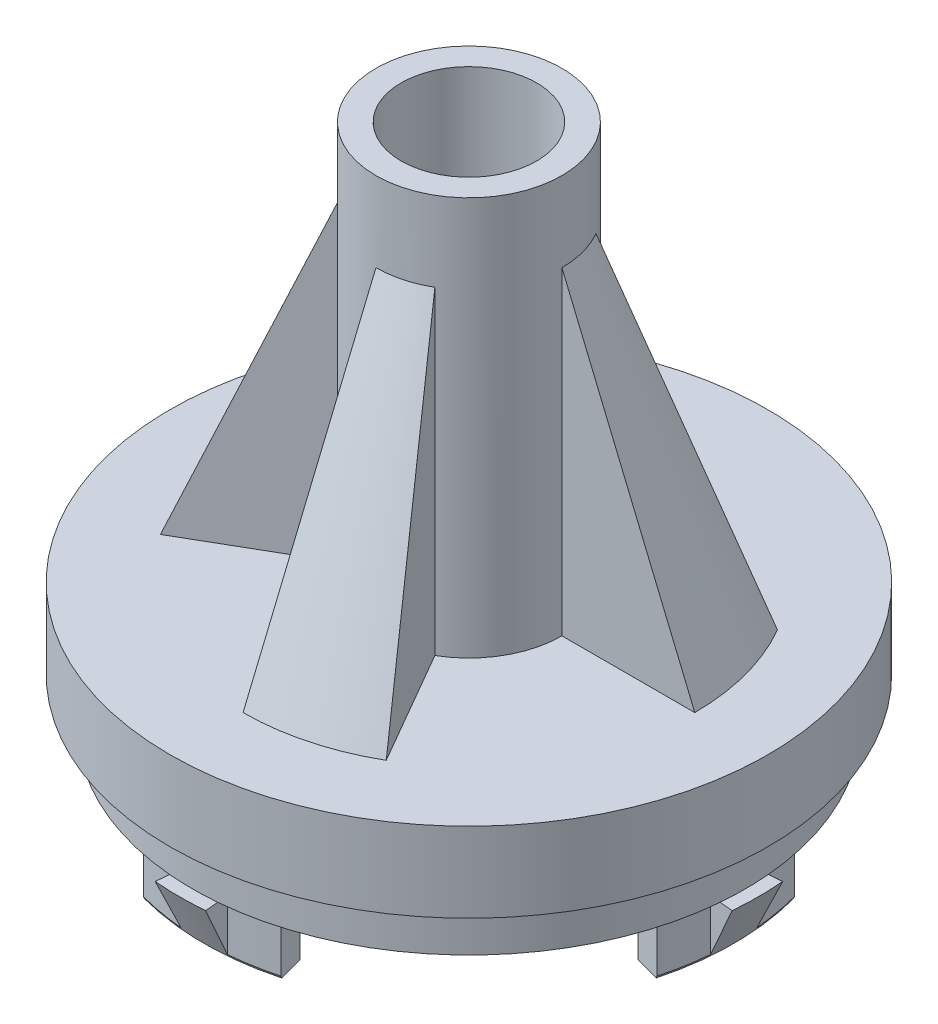
SolidWorks part; units mm, degrees
ref_plane "前视基准面" through (0, 0, 0) normal (0, 0, 1) x (1, 0, 0)
ref_plane "上视基准面" through (0, 0, 0) normal (0, 1, 0) x (1, 0, 0)
ref_plane "右视基准面" through (0, 0, 0) normal (1, 0, 0) x (0, 0, -1)
other "Configuration Table"
sketch "草图1" plane through (0, 0, 0) normal (0, 1, 0) x (1, 0, 0)
  circle A0 centre (0, 0) radius 10.4
  dimension "D1" = 20.8
extrude "凸台-拉伸1" add sketch "草图1" along normal blind 1.8
sketch "草图2" plane through (0, 1.8, 0) normal (0, 1, 0) x (1, 0, 0)
  circle A0 centre (0, 0) radius 11.25
  dimension "D1" = 22.5
extrude "凸台-拉伸2" add sketch "草图2" along normal blind 3
sketch "草图3" plane through (0, 4.8, 0) normal (0, 1, 0) x (1, 0, 0)
  circle A0 centre (0, 0) radius 3.5
  circle A1 centre (0, 0) radius 2.55
  circle A2 centre (0, 0) radius 1.5
  dimension "D1" = 7
  dimension "D2" = 5.1
  dimension "D3" = 3
extrude "凸台-拉伸3" add sketch "草图3" along normal blind 15 contours A0 A1 region at (-3.401, 4.8, 0)
extrude "切除-拉伸2" cut sketch "草图3<4>" against normal up to surface (4.8 mm away) contours A2 up to face at (0, 0, 10.4)
sketch "草图3<4>" plane through (0, 4.8, 0) normal (0, 1, 0) x (1, 0, 0) same geometry as "草图3"
sketch "草图6" plane through (0, 0, 0) normal (1, 0, 0) x (0, 0, -1)
  line L0 (0, 0) -> (0, 11.6571) construction
  line L1 (0, 0) -> (14.4338, 0) construction
  line L2 (3.5, 16.8) -> (8.5, 4.8)
  line L3 (3.5, 4.8) -> (3.5, 19.8) construction
  line L4 (11.25, 4.8) -> (-11.25, 4.8) construction
  line L5 (8.5, 4.8) -> (3.5, 4.8)
  line L6 (3.5, 4.8) -> (3.5, 16.8)
  line L7 (-8.5, 4.8) -> (-3.5, 4.8)
  line L8 (-3.5, 16.8) -> (-8.5, 4.8)
  line L9 (-3.5, 4.8) -> (-3.5, 16.8)
  dimension "D1" = 5
  dimension "D2" = 12
revolve "旋转3" add sketch "草图6" angle 30 about L0 region at (0, 8.8, -5.1667) region at (0, 8.8, 5.1667)
sketch "草图9" plane through (0, 0, 0) normal (0, 0, 1) x (1, 0, 0)
  line L0 (3.5, 4.8) -> (8.5, 4.8)
  line L1 (3.5, 16.8) -> (3.5, 4.8)
  line L2 (8.5, 4.8) -> (3.5, 16.8)
  line L3 (3.5, 4.8) -> (3.5, 19.8) construction
  line L4 (0, 0) -> (0, 22.6974) construction
  line L6 (-8.5, 4.8) -> (-3.5, 16.8)
  line L7 (-3.5, 4.8) -> (-8.5, 4.8)
  line L8 (-3.5, 16.8) -> (-3.5, 4.8)
  dimension "D1" = 5
  dimension "D2" = 12
revolve "旋转4" add sketch "草图9" angle 30 about L4
sketch "草图10" plane through (0, 0, 0) normal (0, -1, 0) x (1, 0, 0)
  line L0 (0, 0) -> (14.3336, 0) construction
  line L1 (0, 0) -> (0, 5.5131) construction
  line L2 (0, 0) -> (10.8585, 0.95)
  line L3 (0, 0) -> (10.8585, -0.95)
  line L4 (0, 0) -> (-0.95, -10.8585)
  line L5 (0, 0) -> (0.95, -10.8585)
  line L6 (0, 0) -> (-10.8585, 0.95)
  line L7 (0, 0) -> (-10.8585, -0.95)
  line L8 (0, 0) -> (0.95, 10.8585)
  line L9 (0, 0) -> (-0.95, 10.8585)
  line L10 (0, 0) -> (10.5286, 2.8211)
  line L11 (0, 0) -> (10.5286, -2.8211)
  line L12 (0, 0) -> (2.8211, -10.5286)
  line L13 (0, 0) -> (-2.8211, -10.5286)
  line L14 (0, 0) -> (-10.5286, -2.8211)
  line L15 (0, 0) -> (-10.5286, 2.8211)
  line L16 (0, 0) -> (-2.8211, 10.5286)
  line L17 (0, 0) -> (2.8211, 10.5286)
  arc A0 (9.6593, 2.5882) -> (9.6593, -2.5882) centre (0, 0) ccw
  arc A1 (10.8585, 0.95) -> (10.8585, -0.95) centre (0, 0) cw
  arc A2 (0.95, -10.8585) -> (-0.95, -10.8585) centre (0, 0) cw
  arc A3 (-10.8585, -0.95) -> (-10.8585, 0.95) centre (0, 0) cw
  arc A4 (-0.95, 10.8585) -> (0.95, 10.8585) centre (0, 0) cw
  circle A5 centre (0, 0) radius 10
  circle A7 centre (0, 0) radius 10.9
  arc A9 (9.9619, 0.8716) -> (9.9619, -0.8716) centre (0, 0) cw
  circle A10 centre (0, 0) radius 9
  arc A11 (10.5286, 2.8211) -> (10.5319, -2.8087) centre (0, 0) cw
  arc A12 (8.6933, 2.3294) -> (8.6933, -2.3294) centre (0, 0) cw
  point P25 (0, 0)
  circle M5 centre (0, 0) radius 10.4
  dimension "D3" = 20
  dimension "D4" = 21.8
  dimension "D5" = 18
  dimension "D1" = 5
  dimension "D6" = 15
  dimension "D2" = 4
  dimension "D7" = 4
extrude "凸台-拉伸4" add sketch "草图10" along normal blind 2 contours A3 L7 L6 M5 | A0 L6 L7 M5 | A10 L6 A0 L7 | A10 L15 A0 L6 | A10 L7 A0 L14 | A10 L9 A0 L16 | A10 L8 A0 L9 | A10 L17 A0 L8 | A0 L8 L9 M5 | A4 L9 L8 M5 | A10 L2 A5 L10 | A10 L3 A5 L2 | A10 L11 A5 L3 | A5 L3 L2 M5 | A1 L2 L3 M5 | A10 L13 A0 L4 | A10 L4 A0 L5 | A10 L5 A0 L12 | A0 L4 L5 M5 | A2 L5 L4 M5 region at (9.3524, 0, 1.6491) region at (9.4967, 0, 0) region at (9.3524, 0, -1.6491) region at (0, 0, -9.4967) region at (-1.6491, 0, -9.3524) region at (1.6491, 0, -9.3524) region at (-9.4967, 0, 0) region at (-9.3524, 0, 1.6491) region at (-9.3524, 0, -1.6491) region at (0, 0, 9.4967) region at (1.6491, 0, 9.3524) region at (-1.6491, 0, 9.3524) region at (10.1884, 0, 0) region at (0, 0, -10.1884) region at (-10.1884, 0, 0) region at (0, 0, 10.1884) region at (10.6384, 0, 0) region at (0, 0, -10.6384) region at (-10.6384, 0, 0) region at (0, 0, 10.6384)
sketch "草图11" plane through (0, 0, 0) normal (0, 0, 1) x (1, 0, 0)
  line L0 (10.9, 0) -> (9.9619, -2)
  line L1 (9.9619, -2) -> (10.9, -2)
  line L2 (10.9, -2) -> (10.9, 0)
  line L3 (0, 0) -> (0, -3.1109) construction
revolve "切除-旋转2" cut sketch "草图11" angle 360 about L3 region at (10.5873, -1.3333, 0)
